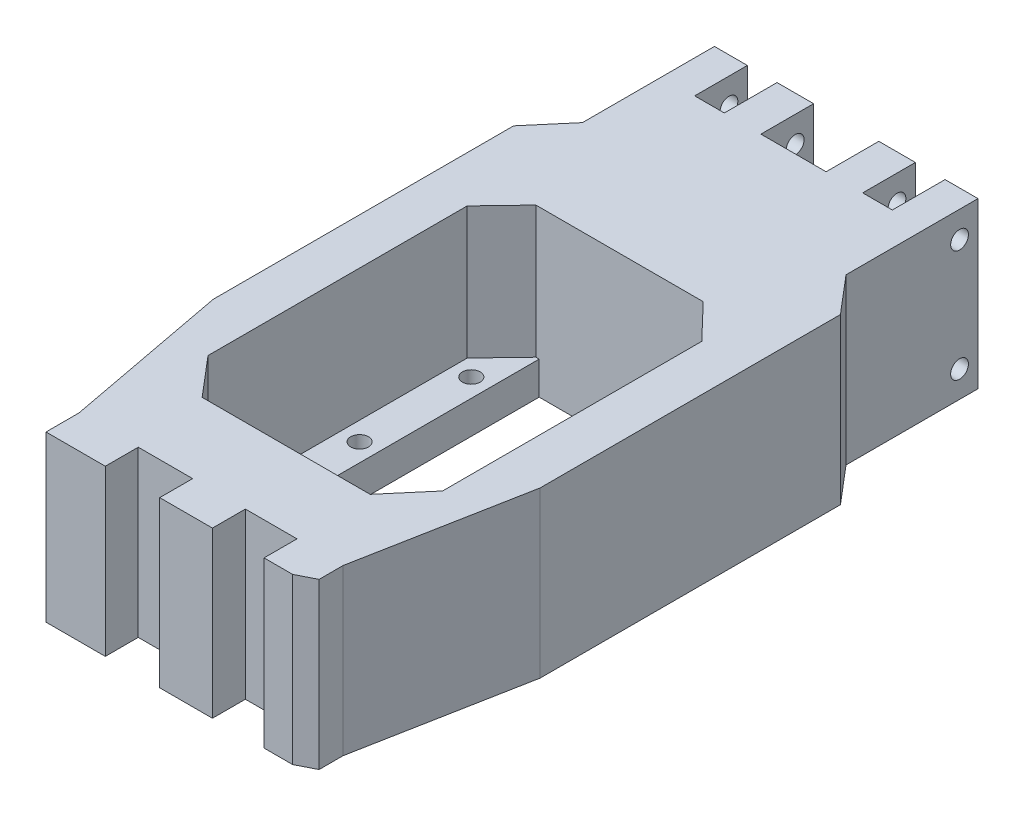
SolidWorks part; units mm, degrees
material "ABS"
ref_plane "Płaszczyzna przednia" through (0, 0, 0) normal (0, 0, 1) x (1, 0, 0)
ref_plane "Płaszczyzna górna" through (0, 0, 0) normal (0, 1, 0) x (1, 0, 0)
ref_plane "Płaszczyzna prawa" through (0, 0, 0) normal (1, 0, 0) x (0, 0, -1)
sketch "Szkic1" plane through (0, 0, 0) normal (0, 1, 0) x (1, 0, 0)
  line L0 (10.0478, 143.7963) -> (14.5478, 143.7963)
  line L1 (-0.4522, 106.3963) -> (-0.4522, 55.3963) construction
  line L2 (-5.3995, 151.7963) -> (-5.3995, 143.7963)
  line L3 (-5.3995, 143.7963) -> (4.4951, 143.7963)
  line L4 (19.5956, 55.3963) -> (-20.5, 55.3963)
  line L5 (-10.9522, 151.7963) -> (-5.3995, 151.7963)
  line L6 (24.3478, 126.118) -> (24.3478, 80.5335)
  line L7 (-10.9522, 151.7963) -> (-10.9522, 143.7963)
  line L8 (14.5478, 143.7963) -> (14.5478, 151.7963)
  line L9 (-12.6522, 117.3963) -> (11.7478, 117.3963)
  line L10 (-20.4522, 131.7671) -> (-25.2522, 126.118)
  line L11 (14.5478, 151.7963) -> (19.5478, 151.7963)
  line L12 (-37.6655, 105.3963) -> (36.761, 105.3963) construction
  line L13 (-0.4522, 105.3963) -> (-0.4522, 211.3963) construction
  line L14 (11.7478, 117.3963) -> (11.7478, 72.3963)
  line L15 (11.7478, 72.3963) -> (-12.6522, 72.3963)
  line L16 (19.5478, 151.7963) -> (19.5478, 131.7671)
  line L17 (-13.1522, 117.3963) -> (12.2478, 117.3963)
  line L18 (-25.2522, 105.3963) -> (24.3478, 105.3963) construction
  line L19 (1.0907, -6.7501) -> (1.0723, -6.7223)
  line L20 (17.3478, 112.0706) -> (17.3478, 72.7401)
  line L21 (-20.4522, 151.7963) -> (-20.4522, 131.7671)
  line L22 (19.5478, 131.7671) -> (24.3478, 126.118)
  line L23 (10.0478, 151.7963) -> (10.0478, 143.7963)
  line L24 (10.0478, 151.7963) -> (4.4951, 151.7963)
  line L25 (17.3478, 72.7401) -> (12.2956, 66.7963)
  line L26 (4.4951, 151.7963) -> (4.4951, 143.7963)
  line L27 (12.2956, 66.7963) -> (-13.2, 66.7963)
  line L28 (12.2478, 117.3963) -> (17.3478, 112.0706)
  line L29 (-13.1522, 117.3963) -> (-18.2522, 112.0706)
  line L30 (-18.2522, 72.7401) -> (-13.2, 66.7963)
  line L31 (-18.2522, 112.0706) -> (-18.2522, 72.7401)
  line L32 (-12.6522, 117.3963) -> (-12.6522, 72.3963)
  line L33 (19.5956, 55.3963) -> (24.3478, 80.5335)
  line L34 (-15.4522, 151.7963) -> (-20.4522, 151.7963)
  line L35 (-15.4522, 143.7963) -> (-15.4522, 151.7963)
  line L36 (1.1229, -6.7586) -> (1.0907, -6.7501)
  line L37 (-10.9522, 143.7963) -> (-15.4522, 143.7963)
  line L38 (-20.5, 55.3963) -> (-25.2522, 80.5335)
  line L39 (-25.2522, 126.118) -> (-25.2522, 80.5335)
  line L46 (-2.1229, -6.7586) -> (-2.0907, -6.7501)
  circle A0 centre (14.5478, 109.8963) radius 1.35
  circle A1 centre (-0.4522, 105.3963) radius 4
  circle A2 centre (14.5, 92.8963) radius 1.35
  circle A3 centre (14.5, 75.8963) radius 1.35
  circle A4 centre (8.0478, 69.5963) radius 1.35
  circle A5 centre (-8.9522, 69.5963) radius 1.35
  circle A7 centre (-15.4044, 75.8963) radius 1.35
  circle A8 centre (-15.4044, 92.8963) radius 1.35
  circle A9 centre (-15.4522, 109.8963) radius 1.35
  point P2 (0, 0)
  point P4 (24.3478, 126.118)
  point P9 (-15.5208, -48.1484)
  point P14 (-0.4522, 156.3785)
  point P18 (-34.2569, 59.805)
  point P22 (-0.4522, 105.3963)
  point P27 (32.5, 54.0178)
  point P34 (-0.4522, 105.3963)
  point P41 (-0.4522, 148.8753)
  point P44 (-0.4522, 211.3963)
  point P45 (-9.988, 152.4054)
  point P47 (-36.488, 132.4054)
  point P71 (-0.4522, 66.7963)
  point P73 (-0.4522, 72.3963)
  point P74 (-0.4522, 117.3963)
  point P80 (-0.4522, 143.7963)
  dimension "D6" = 45
  dimension "D5" = 12.2
  dimension "D8" = 15
  dimension "D4" = 50
  dimension "D12" = 85
  dimension "D13" = 9.3
  dimension "D14" = 7.5
  dimension "D15" = 8
  dimension "D16" = 7
  dimension "D10" = 2.7
  dimension "D21" = 2.8
  dimension "D26" = 2.7
  dimension "D27" = 2.7
  dimension "D35" = 2.7
  dimension "D9" = 8
  dimension "D11" = 17.8
  dimension "D20" = 5
  dimension "D22" = 4.5
  dimension "D36" = 24.5
  dimension "D37" = 41.5
  dimension "D38" = 47.8
  dimension "D39" = 5.3257
  dimension "D40" = 12.7
  dimension "D7" = 12
extrude "Dodanie-wyciągnięcie1" add sketch "Szkic1" along normal blind 5 contours A2 A0 A1 | L4 L6 region at (12.2978, 0, -142.7122) region at (-13.2709, 0, -94.8963)
extrude "Dodanie-wyciągnięcie2" add sketch "Szkic1<3>" along normal blind 25 contours L4 L6 region at (12.2978, 0, -142.7122)
sketch "Szkic1<3>" plane through (0, 0, 0) normal (0, 1, 0) x (1, 0, 0) same geometry as "Szkic1"
sketch "Szkic7" plane through (-20.4522, 0, 0) normal (-1, 0, 0) x (0, 0, 1)
  line L0 (-151.7963, 25) -> (-146.1963, 25)
  line L1 (-151.7963, 25) -> (-131.7671, 25) construction
  line L2 (-151.7963, 12.5) -> (-165.8425, 12.5) construction
  line L3 (-151.7963, 25) -> (-151.7963, 0) construction
  circle A0 centre (-148.9963, 21) radius 1.35
  circle A1 centre (-148.9963, 4) radius 1.35
  point P11 (-158.8194, 12.5)
  dimension "D2" = 2.7
  dimension "D4" = 8.5
  dimension "D1" = 5.6
  dimension "D3" = 2.8
sketch "Szkic6" plane through (0, 25, 0) normal (0, 1, 0) x (1, 0, 0)
  line L14 (-15.5, 159.4692) -> (14.5, 159.4692)
  line L15 (14.5, 159.4692) -> (14.5, 124.3963)
  line L18 (14.5, 124.3963) -> (-15.5, 124.3963)
  line L29 (11.2406, 159.4692) -> (-0.5, 145.434)
  line L30 (-0.5, 137.7414) -> (11.178, 124.3963)
  line L31 (14.5, 155.5728) -> (2.79, 141.5743)
  line L32 (2.79, 141.5743) -> (14.5, 128.1926)
  line L33 (-15.5, 159.4692) -> (-15.5, 124.3963)
  line L38 (-0.5, 137.7414) -> (-12.178, 124.3963)
  line L39 (-3.79, 141.5743) -> (-15.5, 128.1926)
  line L40 (-15.5, 155.5728) -> (-3.79, 141.5743)
  line L41 (-12.2406, 159.4692) -> (-0.5, 145.434)
  line L51 (-0.5, 159.4692) -> (-0.5, 124.3963) construction
  point P48 (12.5825, 161.0733)
  point P51 (-3.79, 141.501)
  point P52 (12.6186, 122.75)
  point P53 (16.4175, 157.8651)
  point P55 (16.3814, 126.0427)
  point P61 (-0.5, 124.3963)
  point P62 (-0.5, 159.4692)
extrude "Wytnij-wyciągnięcie5" [suppressed] cut sketch "Szkic6" against normal through all
sketch "Szkic8" plane through (0, 25, 0) normal (0, 1, 0) x (1, 0, 0)
  line L0 (19.5956, 55.3963) -> (19.5956, 51.7445)
  line L1 (16.9256, 50.3963) -> (12.5956, 50.3963)
  line L2 (12.5956, 50.3963) -> (12.5956, 55.3963)
  line L3 (19.5956, 55.3963) -> (-20.5, 55.3963) construction
  line L4 (12.5956, 55.3963) -> (4.7588, 55.3963)
  line L5 (4.7588, 55.3963) -> (4.7588, 50.3963)
  line L6 (4.7588, 50.3963) -> (-3.2412, 50.3963)
  line L7 (-3.2412, 50.3963) -> (-3.2412, 55.3963)
  line L8 (-3.2412, 55.3963) -> (-11.5, 55.3963)
  line L9 (-11.5, 55.3963) -> (-11.5, 50.3963)
  line L10 (-11.5, 50.3963) -> (-20.5, 50.3963)
  line L11 (-20.5, 50.3963) -> (-20.5, 55.3963)
  line L12 (19.5956, 55.3963) -> (-20.5, 55.3963)
  line L13 (19.5956, 51.7445) -> (16.9256, 50.3963)
  line L34 (-20.4522, 131.7671) -> (-25.2522, 126.118)
  line L35 (-25.2522, 126.118) -> (-25.2522, 80.5335)
  line L36 (-25.2522, 80.5335) -> (-20.5, 55.3963)
  line L37 (-20.5, 55.3963) -> (19.5956, 55.3963)
  line L38 (19.5956, 55.3963) -> (24.3478, 80.5335)
  line L39 (24.3478, 80.5335) -> (24.3478, 126.118)
  line L40 (24.3478, 126.118) -> (19.5478, 131.7671)
  line L41 (19.5478, 131.7671) -> (19.5478, 151.7963)
  line L42 (19.5478, 151.7963) -> (14.5478, 151.7963)
  line L43 (14.5478, 151.7963) -> (14.5478, 143.7963)
  line L44 (14.5478, 143.7963) -> (10.0478, 143.7963)
  line L45 (10.0478, 143.7963) -> (10.0478, 151.7963)
  line L46 (10.0478, 151.7963) -> (4.4951, 151.7963)
  line L47 (4.4951, 151.7963) -> (4.4951, 143.7963)
  line L48 (4.4951, 143.7963) -> (-5.3995, 143.7963)
  line L49 (-5.3995, 143.7963) -> (-5.3995, 151.7963)
  line L50 (-5.3995, 151.7963) -> (-10.9522, 151.7963)
  line L51 (-10.9522, 151.7963) -> (-10.9522, 143.7963)
  line L52 (-10.9522, 143.7963) -> (-15.4522, 143.7963)
  line L53 (-15.4522, 143.7963) -> (-15.4522, 151.7963)
  line L54 (-15.4522, 151.7963) -> (-20.4522, 151.7963)
  line L55 (-20.4522, 151.7963) -> (-20.4522, 131.7671)
  line L56 (-20.4522, 131.7671) -> (-25.2522, 126.118)
  line L57 (-25.2522, 126.118) -> (-25.2522, 80.5335)
  line L58 (-25.2522, 80.5335) -> (-20.5, 55.3963)
  line L60 (19.5956, 55.3963) -> (24.3478, 80.5335)
  line L61 (24.3478, 80.5335) -> (24.3478, 126.118)
  line L62 (24.3478, 126.118) -> (19.5478, 131.7671)
  line L63 (19.5478, 131.7671) -> (19.5478, 151.7963)
  line L64 (19.5478, 151.7963) -> (14.5478, 151.7963)
  line L65 (14.5478, 151.7963) -> (14.5478, 143.7963)
  line L66 (14.5478, 143.7963) -> (10.0478, 143.7963)
  line L67 (10.0478, 143.7963) -> (10.0478, 151.7963)
  line L68 (10.0478, 151.7963) -> (4.4951, 151.7963)
  line L69 (4.4951, 151.7963) -> (4.4951, 143.7963)
  line L70 (4.4951, 143.7963) -> (-5.3995, 143.7963)
  line L71 (-5.3995, 143.7963) -> (-5.3995, 151.7963)
  line L72 (-5.3995, 151.7963) -> (-10.9522, 151.7963)
  line L73 (-10.9522, 151.7963) -> (-10.9522, 143.7963)
  line L74 (-10.9522, 143.7963) -> (-15.4522, 143.7963)
  line L75 (-15.4522, 143.7963) -> (-15.4522, 151.7963)
  line L76 (-15.4522, 151.7963) -> (-20.4522, 151.7963)
  line L77 (-20.4522, 151.7963) -> (-20.4522, 131.7671)
  point P1 (19.5956, 50.3963)
  line M75 (-20.5, 55.3963) -> (19.5956, 55.3963)
  dimension "D1" = 5
  dimension "D2" = 7
  dimension "D3" = 8
  dimension "D4" = 9
  dimension "D5" = 0
  dimension "D6" = 153.21
  dimension "D7" = 4.33
extrude "Dodanie-wyciągnięcie3" add sketch "Szkic8" against normal blind 25 contours L0 L12 L2 L1 | L5 L12 L7 L6 | L9 L12 L11 L10 | L13 L0 L2 L1 M75 region at (15.9541, 25, -53.0075) region at (0.7588, 25, -52.8963) region at (-16, 25, -52.8963)
sketch "Szkic9" [suppressed] plane through (-20.5, 0, 0) normal (-1, 0, 0) x (0, 0, 1)
  circle A0 centre (-169.1445, 11.5841) radius 3.3688
extrude "Wytnij-wyciągnięcie8" cut sketch "Szkic7" against normal through all contours A0 | A1 region at (-20.4522, 21, -148.9963) region at (-20.4522, 4, -148.9963)
